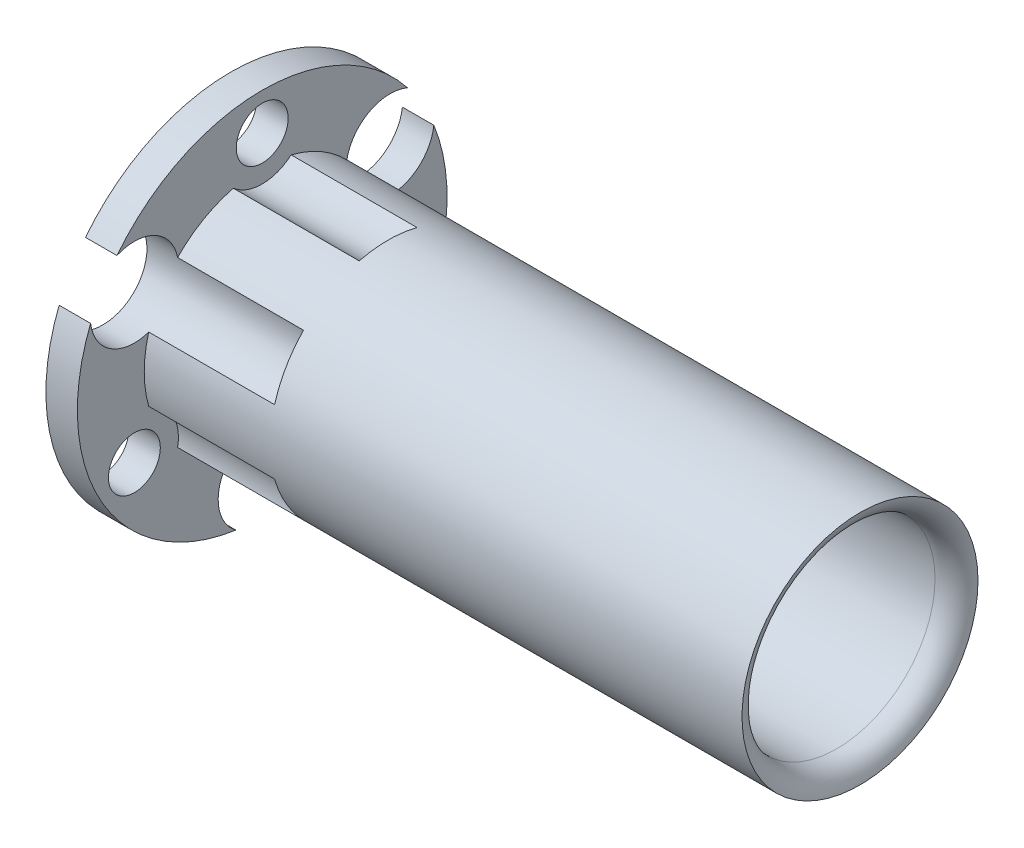
SolidWorks part; units mm, degrees
ref_plane "Front Plane" through (0, 0, 0) normal (0, 0, 1) x (1, 0, 0)
ref_plane "Top Plane" through (0, 0, 0) normal (0, 1, 0) x (1, 0, 0)
ref_plane "Right Plane" through (0, 0, 0) normal (1, 0, 0) x (0, 0, -1)
sketch "Sketch1" plane through (0, 0, 0) normal (1, 0, 0) x (0, 0, -1)
  line L0 (0, 9.385) -> (0, 0) construction
  line L1 (0, 0) -> (0, -9.385) construction
  circle A0 centre (0, 0) radius 6.25
  circle A1 centre (0, 0) radius 11.75
  circle A2 centre (0, 9.385) radius 1.65
  circle A3 centre (8.1276, -4.6925) radius 1.65
  circle A4 centre (-8.1276, -4.6925) radius 1.65
  circle A8 centre (0, 0) radius 7.5
  circle A9 centre (0, -9.385) radius 2.8
  circle A10 centre (-8.1276, -4.6925) radius 2.8
  circle A11 centre (-8.1276, 4.6925) radius 2.8
  circle A12 centre (0, 9.385) radius 2.8
  circle A13 centre (8.1276, 4.6925) radius 2.8
  circle A14 centre (8.1276, -4.6925) radius 2.8
  point P18 (0, 0)
  point P19 (0, 0)
  dimension "D2" = 3.3
  dimension "D3" = 23.5
  dimension "D4" = 12.5
  dimension "D6" = 1.25
  dimension "D8" = 6
  dimension "D7" = 5.6
  dimension "D1" = 9.385
  dimension "D5" = 3
extrude "Boss-Extrude1" add sketch "Sketch1" along normal blind 2 contours A11 A1 A10 A8 | A14 A8 A13 A12 A11 A10 A9 A0 | A12 A1 A11 A8 | A13 A1 A12 A8 | A14 A1 A13 A8 | A14 A8 A9 A1 | A10 A1 A9 A8 | A8 A10 | A8 A9 | A8 A14 | A8 A13 | A8 A12 | A8 A11 | A1 A14 A8 A3 | A8 A10 A1 A4 | A1 A12 A8 A2 region at (0, 0, -9.8051) region at (0, -5.8357, -10.1076) region at (0, 8.4915, -4.9025) region at (0, 3.5422, -6.1352) region at (0, 1.0036, -7.2217) region at (0, -8.4915, -4.9025) region at (0, -3.5422, -6.1352) region at (0, 10.609, -2.4383) region at (0, 8.4915, 4.9025) region at (0, 7.0844, 0) region at (0, -8.4915, 4.9025) region at (0, -7.0844, 0) region at (0, -5.8357, 10.1076) region at (0, 0, 9.8051) region at (0, 3.5422, 6.1352) region at (0, -3.5422, 6.1352)
extrude "Boss-Extrude2" add sketch "Sketch1<3>" along normal blind 40 contours A8 A0 | A8 A11 | A8 A10 | A8 A9 | A8 A14 | A8 A13 | A8 A12 region at (0, 3.5422, -6.1352) region at (0, 1.0036, -7.2217) region at (0, -3.5422, -6.1352) region at (0, 7.0844, 0) region at (0, -7.0844, 0) region at (0, 3.5422, 6.1352) region at (0, -3.5422, 6.1352)
sketch "Sketch1<3>" plane through (0, 0, 0) normal (1, 0, 0) x (0, 0, -1) same geometry as "Sketch1"
extrude "Cut-Extrude2" cut sketch "Sketch1<4>" along normal blind 8 from surface contours A8 A9 A1 | A8 A9 | A8 A10 | A8 A14 | A8 A13 | A8 A12 | A8 A11 region at (0, 3.5422, -6.1352) region at (0, -3.5422, -6.1352) region at (0, -9.5142, 0) region at (0, 7.0844, 0) region at (0, -7.0844, 0) region at (0, 3.5422, 6.1352) region at (0, -3.5422, 6.1352) starting at face at (2, -4.6925, 6.4776)
sketch "Sketch1<4>" plane through (0, 0, 0) normal (1, 0, 0) x (0, 0, -1) same geometry as "Sketch1"
extrude "Cut-Extrude3" cut sketch "Sketch1<5>" against normal through all from surface contours A8 A9 | A8 A13 | A8 A11 region at (0, 3.5422, -6.1352) region at (0, -7.0844, 0) region at (0, 3.5422, 6.1352) starting at face at (2, 3.5213, 6.099)
sketch "Sketch1<5>" plane through (0, 0, 0) normal (1, 0, 0) x (0, 0, -1) same geometry as "Sketch1"
fillet "Fillet1" radius 1.5 1 edges at (40, 0, -6.25)
